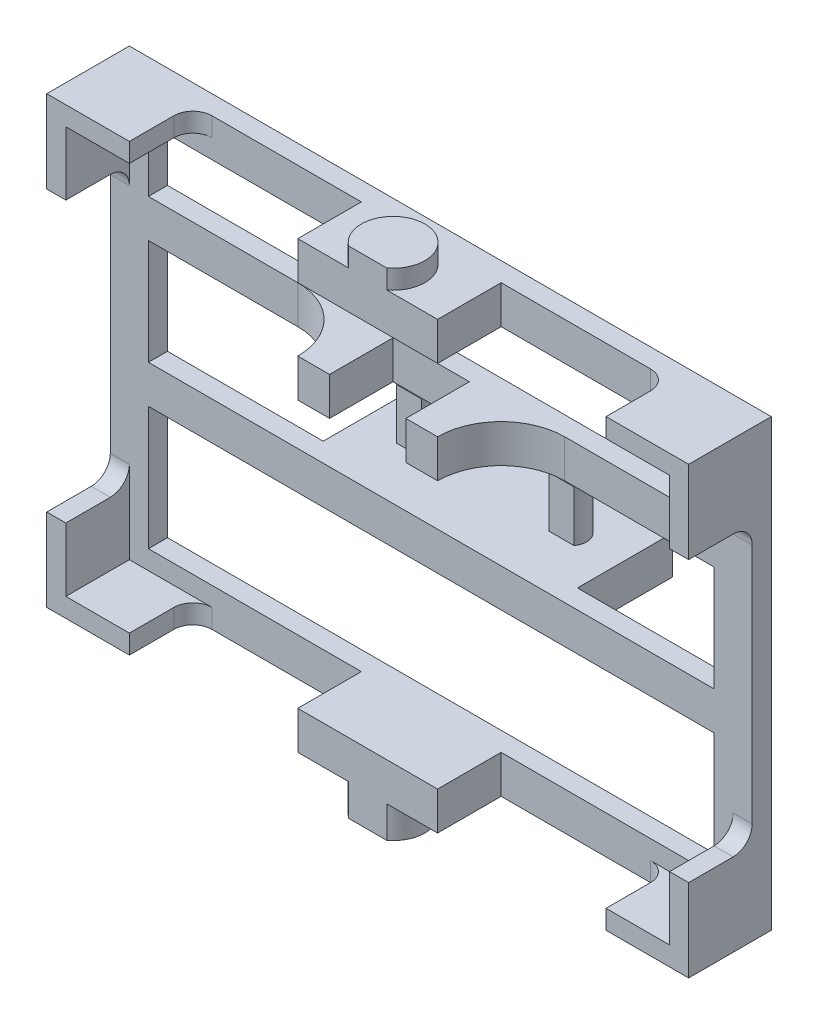
SolidWorks part; units mm, degrees
ref_plane "Alzado" through (0, 0, 0) normal (0, 0, 1) x (1, 0, 0)
ref_plane "Planta" through (0, 0, 0) normal (0, 1, 0) x (1, 0, 0)
ref_plane "Vista lateral" through (0, 0, 0) normal (1, 0, 0) x (0, 0, -1)
sketch "Croquis1" plane through (0, 0, 0) normal (0, 0, 1) x (1, 0, 0)
  line L0 (-3, 67) -> (98, 67)
  line L1 (0, 0) -> (95, 0) construction
  line L2 (0, 0) -> (0, 64) construction
  line L3 (0, 64) -> (95, 64) construction
  line L4 (95, 0) -> (95, 64) construction
  line L5 (98, -3) -> (98, 67)
  line L6 (-3, -3) -> (98, -3)
  line L7 (-3, -3) -> (-3, 67)
  line L8 (3, 61) -> (92, 61)
  line L9 (92, 3) -> (92, 61)
  line L10 (3, 3) -> (92, 3)
  line L11 (3, 3) -> (3, 61)
  line L12 (0, 32) -> (95, 32) construction
  line L13 (3, 28.4) -> (92, 28.4)
  line L14 (3, 45) -> (92, 45)
  line L15 (0, 28.4) -> (95, 28.4) construction
  line L16 (0, 45) -> (95, 45) construction
  line L18 (3, 45) -> (92, 45)
  line L19 (3, 45) -> (3, 51)
  line L20 (3, 51) -> (92, 51)
  line L21 (92, 45) -> (92, 51)
  line L22 (3, 28.4) -> (92, 28.4)
  line L23 (3, 28.4) -> (3, 22.4)
  line L24 (3, 22.4) -> (92, 22.4)
  line L25 (92, 28.4) -> (92, 22.4)
  dimension "D1" = 95
  dimension "D2" = 64
  dimension "D7" = 6
  dimension "D8" = 6
  dimension "D3" = 3
  dimension "D4" = 3
  dimension "D5" = 3.6
  dimension "D6" = 13
extrude "Saliente-Extruir1" add sketch "Croquis1" along normal blind 3 contours L7 L6 L5 L0 L10 L11 L8 L9 | L20 L11 L14 L9 | L11 L24 L9 L13 region at (47.5, 65.7711, 0) region at (47.5, 48, 0) region at (47.5, 25.4, 0)
sketch "Croquis2" plane through (0, 0, 3) normal (0, 0, 1) x (1, 0, 0)
  line L0 (98, 32) -> (-3, 32) construction
  line L3 (85, 67) -> (98, 67)
  line L5 (47.5, 67) -> (47.5, -3) construction
  line L6 (98, -3) -> (98, 67) construction
  line L8 (98, 67) -> (98, 54)
  line L9 (98, 54) -> (95, 54)
  line L10 (95, 54) -> (95, 64)
  line L11 (95, 64) -> (85, 64)
  line L12 (85, 64) -> (85, 67)
  line L13 (10, 64) -> (10, 67)
  line L14 (0, 64) -> (10, 64)
  line L15 (0, 54) -> (0, 64)
  line L16 (-3, 54) -> (0, 54)
  line L17 (-3, 67) -> (-3, 54)
  line L18 (10, 67) -> (-3, 67)
  line L19 (10, -3) -> (-3, -3)
  line L20 (-3, -3) -> (-3, 10)
  line L21 (-3, 10) -> (0, 10)
  line L22 (0, 10) -> (0, 0)
  line L23 (0, 0) -> (10, 0)
  line L24 (10, 0) -> (10, -3)
  line L25 (85, 0) -> (85, -3)
  line L26 (95, 0) -> (85, 0)
  line L27 (95, 10) -> (95, 0)
  line L28 (98, 10) -> (95, 10)
  line L29 (98, -3) -> (98, 10)
  line L30 (85, -3) -> (98, -3)
  line L31 (-3, -3) -> (-3, 67) construction
  line L32 (-3, -3) -> (98, -3) construction
  line L33 (-3, 67) -> (98, 67) construction
  dimension "D1" = 3
  dimension "D2" = 10
extrude "Saliente-Extruir2" add sketch "Croquis2" along normal blind 10
sketch "Croquis3" plane through (0, 0, 3) normal (0, 0, 1) x (1, 0, 0)
  line L0 (47.5, 67) -> (47.5, 45) construction
  line L1 (10, 67) -> (85, 67) construction
  line L2 (3, 45) -> (92, 45) construction
  line L3 (3, 51) -> (92, 51) construction
  line L4 (41.5, 45) -> (53.5, 45) construction
  line L5 (41.5, 45) -> (41.5, 51) construction
  line L6 (41.5, 51) -> (53.5, 51) construction
  line L7 (53.5, 45) -> (53.5, 51) construction
  line L8 (41.5, 45) -> (41.5, 51) construction
  line L9 (53.5, 45) -> (58.5, 45)
  line L10 (53.5, 45) -> (53.5, 51)
  line L11 (53.5, 51) -> (58.5, 51)
  line L12 (58.5, 45) -> (58.5, 51)
  line L13 (36.5, 45) -> (36.5, 51)
  line L14 (41.5, 51) -> (36.5, 51)
  line L15 (41.5, 45) -> (41.5, 51)
  line L16 (41.5, 45) -> (36.5, 45)
  point P10 (47.5, 45)
  dimension "D1" = 12
  dimension "D2" = 5
extrude "Saliente-Extruir3" add sketch "Croquis3" along normal blind 10
fillet "Redondeo1" radius 10 2 edges at (36.5, 48, 3) (58.5, 48, 3)
fillet "Redondeo2" radius 3 8 edges at (-1.5, 10, 3) (10, -1.5, 3) (96.5, 10, 3) (85, -1.5, 3) (85, 65.5, 3) (96.5, 54, 3) (10, 65.5, 3) (-1.5, 54, 3)
ref_plane "plano de rotacion" through (0, 31, 0) normal (0, 1, 0) x (1, 0, 0)
sketch "Croquis4" plane through (0, 31, 0) normal (0, 1, 0) x (1, 0, 0)
  line L0 (41.5, -3) -> (53.5, -3) construction
  line L1 (47.5, -9) -> (47.5, 9.6814) construction
  circle A0 centre (47.5, -9) radius 10
  circle A1 centre (59.5, 7) radius 10
  circle A2 centre (35.5, 7) radius 10
  circle A3 centre (59.5, 7) radius 12 construction
  circle A4 centre (35.5, 7) radius 12 construction
  point P4 (47.5, -3)
  dimension "D2" = 20
  dimension "D4" = 24
  dimension "D5" = 24
  dimension "D1" = 6
sketch "Croquis5" plane through (0, 0, 0) normal (0, 0, -1) x (-1, 0, 0)
  line L0 (-3, 28.4) -> (-92, 28.4) construction
  line L1 (-27.5, 28.4) -> (-67.5, 28.4)
  line L2 (-27.5, 28.4) -> (-27.5, 22.4)
  line L3 (-27.5, 22.4) -> (-67.5, 22.4)
  line L4 (-67.5, 28.4) -> (-67.5, 22.4)
  line L5 (-3, 22.4) -> (-92, 22.4) construction
  point P8 (-47.5, 28.4)
  point P9 (-47.5, 28.4)
  dimension "D1" = 40
extrude "Saliente-Extruir4" add sketch "Croquis5" along normal blind 15
sketch "Croquis6" plane through (0, 28.4, 0) normal (0, 1, 0) x (1, 0, 0)
  circle A0 centre (35.5, 7) radius 2.45
  circle A1 centre (59.5, 7) radius 2.45
  circle A2 centre (35.5, 7) radius 10 construction
  circle A3 centre (59.5, 7) radius 10 construction
  dimension "D1" = 4.9
  dimension "D2" = 4.9
extrude "Saliente-Extruir5" add sketch "Croquis6" along normal blind 8
sketch "Croquis7" plane through (0, 0, 3) normal (0, 0, 1) x (1, 0, 0)
  line L0 (13, -3) -> (82, -3) construction
  line L1 (36.5, -3) -> (58.5, -3)
  line L2 (36.5, -3) -> (36.5, 3)
  line L3 (36.5, 3) -> (58.5, 3)
  line L4 (58.5, -3) -> (58.5, 3)
  line L5 (3, 3) -> (92, 3) construction
  line L6 (3, 61) -> (92, 61) construction
  line L7 (58.5, 61) -> (36.5, 61)
  line L8 (58.5, 61) -> (58.5, 67)
  line L9 (58.5, 67) -> (36.5, 67)
  line L10 (36.5, 61) -> (36.5, 67)
  line L11 (13, 67) -> (82, 67) construction
  line L12 (58.5, 45) -> (58.5, 51) construction
  point P16 (47.5, 3)
extrude "Saliente-Extruir6" add sketch "Croquis7" along normal through all
sketch "Croquis8" plane through (0, -3, 0) normal (0, -1, 0) x (1, 0, 0)
  circle A0 centre (47.5, 9) radius 5
  dimension "D1" = 10
extrude "Saliente-Extruir7" add sketch "Croquis8" along normal blind 5
sketch "Croquis9" plane through (0, 3, 0) normal (0, 1, 0) x (1, 0, 0)
  line L0 (58.5, -13) -> (58.5, -3) construction
  line L1 (36.5, -13) -> (58.5, -13)
  line L2 (36.5, -13) -> (36.5, -32.4468)
  line L3 (36.5, -32.4468) -> (58.5, -32.4468)
  line L4 (58.5, -13) -> (58.5, -32.4468)
extrude "Cortar-Extruir1" cut sketch "Croquis9" against normal through all
mirror "Simetría1" about plane through (0, 31, 0) normal (0, 1, 0) of "Cortar-Extruir1", "Saliente-Extruir7"
sketch "Croquis10" plane through (0, 36.4, 0) normal (0, 1, 0) x (1, 0, 0)
  line L1 (61.4715, 5.5) -> (33.209, 5.5)
  line L2 (61.4715, 5.5) -> (61.4715, 2.1099)
  line L3 (61.4715, 2.1099) -> (33.209, 2.1099)
  line L4 (33.209, 5.5) -> (33.209, 2.1099)
  dimension "D1" = 1.5
extrude "Cortar-Extruir2" cut sketch "Croquis10" against normal up to surface (8 mm away) up to face at (59.5, 28.4, -4.55)
